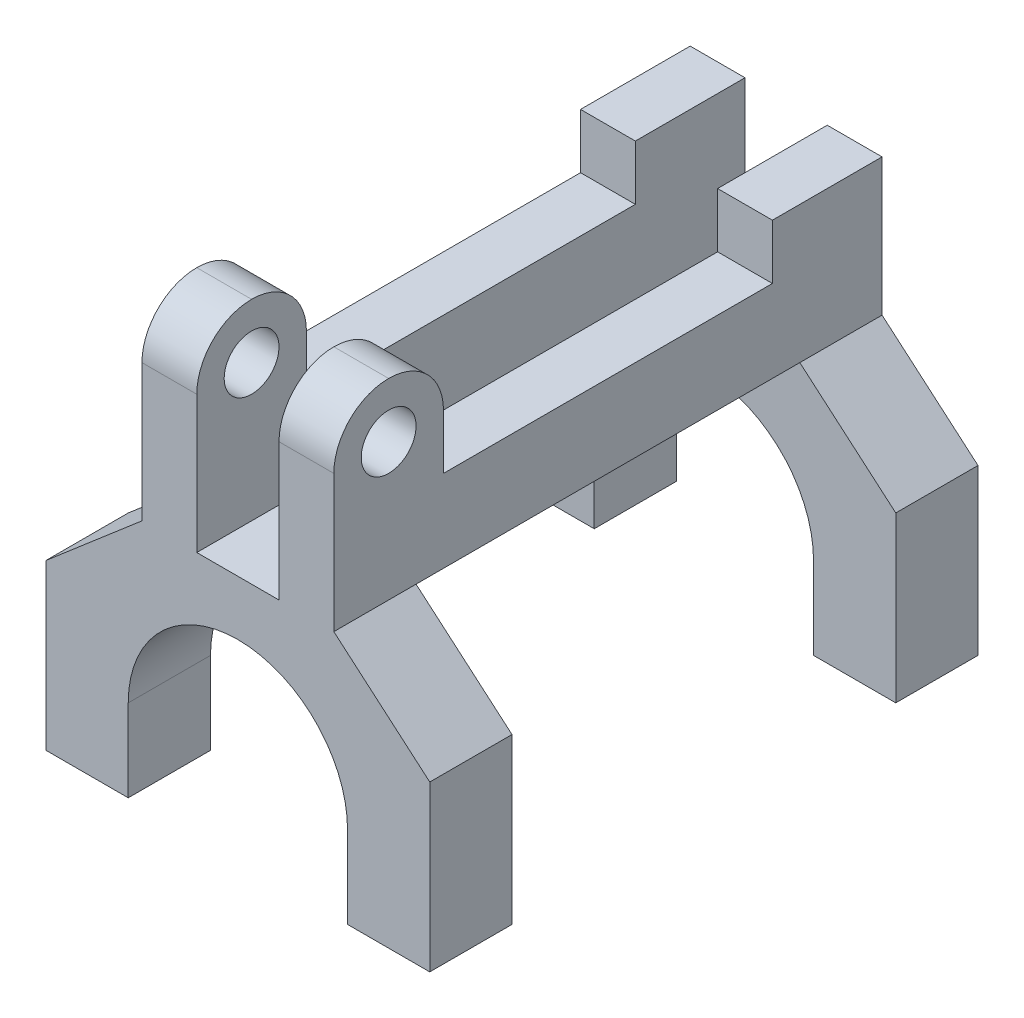
SolidWorks part; units mm, degrees
ref_plane "Front Plane" through (0, 0, 0) normal (0, 0, 1) x (1, 0, 0)
ref_plane "Top Plane" through (0, 0, 0) normal (0, 1, 0) x (1, 0, 0)
ref_plane "Right Plane" through (0, 0, 0) normal (1, 0, 0) x (0, 0, -1)
sketch "Sketch2" plane through (0, 0, 0) normal (0, 0, 1) x (1, 0, 0)
  line L0 (0, 0) -> (19.05, 0)
  line L1 (19.05, 0) -> (19.05, 19.05)
  line L2 (69.85, 19.05) -> (69.85, 0)
  line L3 (69.85, 0) -> (88.9, 0)
  line L4 (88.9, 0) -> (88.9, 38.1)
  line L5 (88.9, 38.1) -> (66.675, 57.15)
  line L6 (66.675, 57.15) -> (22.225, 57.15)
  line L7 (22.225, 57.15) -> (0, 38.1)
  line L8 (0, 38.1) -> (0, 0)
  arc A0 (19.05, 19.05) -> (69.85, 19.05) centre (44.45, 19.05) cw
  dimension "D1" = 25.4
  dimension "D2" = 19.05
  dimension "D3" = 19.05
  dimension "D4" = 88.9
  dimension "D5" = 38.1
  dimension "D6" = 38.1
  dimension "D7" = 19.05
  dimension "D8" = 22.225
  dimension "D9" = 22.225
  dimension "D10" = 19.05
extrude "Boss-Extrude1" add sketch "Sketch2" against normal blind 127
sketch "Sketch3" plane through (88.9, 0, 0) normal (1, 0, 0) x (0, 0, -1)
  line L0 (127, 0) -> (0, 0) construction
  line L1 (19.05, 0) -> (107.95, 0)
  line L2 (19.05, 0) -> (19.05, 57.15)
  line L3 (19.05, 57.15) -> (107.95, 57.15)
  line L4 (107.95, 0) -> (107.95, 57.15)
  line L5 (127, 57.15) -> (0, 57.15) construction
  line L6 (0, 0) -> (0, 38.1) construction
  line L7 (127, 0) -> (127, 38.1) construction
  dimension "D1" = 19.05
  dimension "D2" = 19.05
extrude "Cut-Extrude1" cut sketch "Sketch3" against normal through all
sketch "Sketch5" plane through (0, 0, 0) normal (0, 0, 1) x (1, 0, 0)
  line L0 (22.225, 57.15) -> (22.225, 101.6)
  line L1 (22.225, 101.6) -> (66.675, 101.6)
  line L3 (22.225, 57.15) -> (66.675, 57.15)
  line L4 (66.675, 57.15) -> (66.675, 101.6)
  dimension "D1" = 44.45
  dimension "D2" = 44.45
extrude "Boss-Extrude2" add sketch "Sketch5" against normal blind 127
sketch "Sketch6" plane through (66.675, 0, 0) normal (1, 0, 0) x (0, 0, -1)
  line L0 (127, 88.9) -> (101.6, 88.9)
  line L1 (127, 57.15) -> (127, 101.6) construction
  line L2 (101.6, 88.9) -> (101.6, 76.2)
  line L3 (101.6, 76.2) -> (25.4, 76.2)
  line L4 (25.4, 76.2) -> (25.4, 101.6)
  line L5 (127, 101.6) -> (0, 101.6) construction
  line L6 (25.4, 101.6) -> (127, 101.6)
  line L7 (127, 101.6) -> (127, 88.9)
  dimension "D1" = 12.7
  dimension "D2" = 25.4
  dimension "D3" = 31.75
  dimension "D4" = 76.2
extrude "Cut-Extrude2" cut sketch "Sketch6" against normal through all
fillet "Fillet1" radius 12.7 2 edges at (44.45, 101.6, 0) (44.45, 101.6, -25.4)
sketch "Sketch8" plane through (66.675, 0, 0) normal (1, 0, 0) x (0, 0, -1)
  circle A0 centre (12.7, 88.9) radius 6.35
  dimension "D1" = 12.7
  dimension "D2" = 12.7
  dimension "D3" = 0
extrude "Cut-Extrude3" cut sketch "Sketch8" against normal through all contours A0
sketch "Sketch9" plane through (0, 0, 0) normal (0, 0, 1) x (1, 0, 0)
  line L0 (22.225, 88.9) -> (22.225, 57.15) construction
  line L1 (34.925, 57.15) -> (53.975, 57.15)
  line L2 (34.925, 57.15) -> (34.925, 101.6)
  line L3 (34.925, 101.6) -> (53.975, 101.6)
  line L4 (53.975, 57.15) -> (53.975, 101.6)
  arc A0 (69.85, 19.05) -> (19.05, 19.05) centre (44.45, 19.05) ccw construction
  dimension "D1" = 19.05
  dimension "D2" = 12.7
  dimension "D3" = 44.45
  dimension "D4" = 38.1
extrude "Cut-Extrude4" cut sketch "Sketch9" against normal through all
